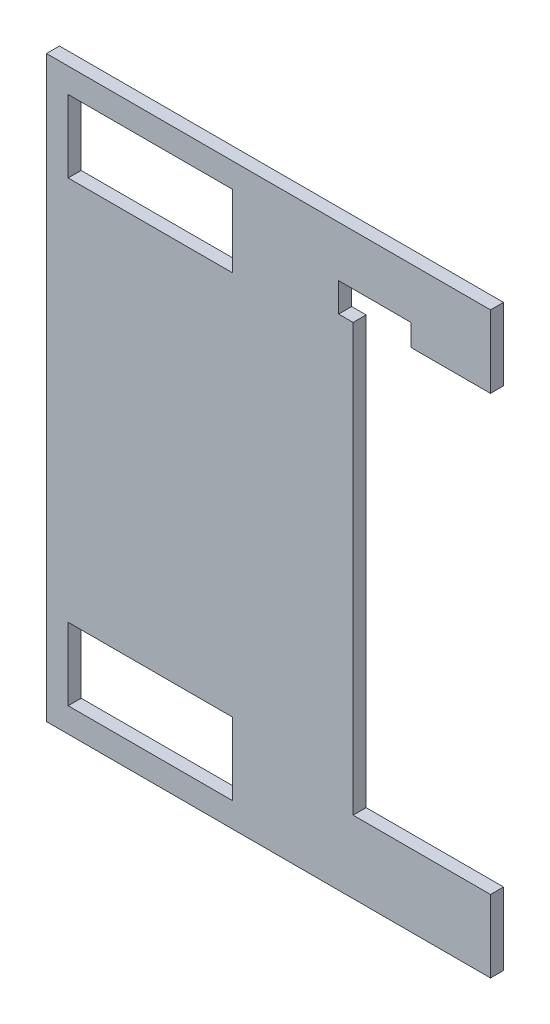
SolidWorks part; units mm, degrees
material "Pine"
ref_plane "Front Plane" through (0, 0, 0) normal (0, 0, 1) x (1, 0, 0)
ref_plane "Top Plane" through (0, 0, 0) normal (0, 1, 0) x (1, 0, 0)
ref_plane "Right Plane" through (0, 0, 0) normal (1, 0, 0) x (0, 0, -1)
sketch "Sketch1" plane through (0, 0, 0) normal (0, 0, 1) x (1, 0, 0)
  line L0 (-16.8129, -74.6) -> (-16.8129, 325.4)
  line L1 (-16.8129, 325.4) -> (-323.8122, 325.4)
  line L2 (-323.8122, 325.4) -> (-323.8122, -74.6)
  line L3 (-323.8122, -74.6) -> (-16.8129, -74.6)
  line L9 (-308.8122, 308.4) -> (-195.1729, 308.4)
  line L10 (-308.8122, 308.4) -> (-308.8122, 258.4)
  line L11 (-308.8122, 258.4) -> (-195.1729, 258.4)
  line L12 (-195.1729, 308.4) -> (-195.1729, 258.4)
  line L13 (-308.8122, 308.4) -> (-195.1729, 258.4) construction
  line L14 (-308.8122, 258.4) -> (-195.1729, 308.4) construction
  line L18 (-308.8122, -57.6) -> (-195.1729, -57.6)
  line L19 (-308.8122, -57.6) -> (-308.8122, -7.6)
  line L20 (-308.8122, -7.6) -> (-195.1729, -7.6)
  line L21 (-195.1729, -57.6) -> (-195.1729, -7.6)
  line L22 (-308.8122, -57.6) -> (-195.1729, -7.6) construction
  line L23 (-308.8122, -7.6) -> (-195.1729, -57.6) construction
  point P16 (-251.9926, 283.4)
  point P27 (-251.9926, -32.6)
  dimension "D2" = 50
  dimension "D3" = 17
  dimension "D5" = 15
  dimension "D6" = 15
extrude "Boss-Extrude1" add sketch "Sketch1" along normal blind 9
sketch "Sketch2" plane through (0, 0, 0) normal (0, 0, -1) x (-1, 0, 0)
  line L0 (111.8129, -24.6) -> (111.8129, 275.4)
  line L1 (16.8129, 325.4) -> (111.8129, 325.4)
  line L2 (16.8129, 325.4) -> (16.8129, 275.4)
  line L3 (16.8129, 275.4) -> (111.8129, 275.4)
  line L4 (111.8129, 325.4) -> (111.8129, 275.4)
  line L5 (16.8129, 325.4) -> (111.8129, 275.4) construction
  line L6 (16.8129, 275.4) -> (111.8129, 325.4) construction
  line L7 (16.8129, -74.6) -> (111.8129, -74.6)
  line L8 (16.8129, -74.6) -> (16.8129, -24.6)
  line L9 (16.8129, -24.6) -> (111.8129, -24.6)
  line L10 (111.8129, -74.6) -> (111.8129, -24.6)
  line L11 (16.8129, -74.6) -> (111.8129, -24.6) construction
  line L12 (16.8129, -24.6) -> (111.8129, -74.6) construction
  point P4 (64.3129, 300.4)
  point P10 (64.3129, -49.6)
  line M11 (16.8129, 325.4) -> (16.8129, -74.6)
  dimension "D1" = 50
  dimension "D2" = 50
  dimension "D3" = 95
extrude "Cut-Extrude1" cut sketch "Sketch2" against normal through all contours L9 L0 L3 M11 region at (-64.3129, 125.4, 0)
sketch "Sketch3" plane through (0, 0, 0) normal (0, 0, -1) x (-1, 0, 0)
  line L1 (111.8129, 275.4) -> (71.8129, 275.4)
  line L2 (111.8129, 275.4) -> (111.8129, 290.4)
  line L3 (111.8129, 290.4) -> (71.8129, 290.4)
  line L4 (71.8129, 275.4) -> (71.8129, 290.4)
  dimension "D1" = 40
  dimension "D2" = 15
extrude "Cut-Extrude2" cut sketch "Sketch3" against normal blind 10
sketch "Sketch4" plane through (0, 0, 0) normal (0, 0, -1) x (-1, 0, 0)
  line L1 (111.8129, 290.4) -> (121.8129, 290.4)
  line L2 (111.8129, 290.4) -> (111.8129, 270.4)
  line L3 (111.8129, 270.4) -> (121.8129, 270.4)
  line L4 (121.8129, 290.4) -> (121.8129, 270.4)
  dimension "D1" = 10
  dimension "D2" = 20
extrude "Cut-Extrude3" cut sketch "Sketch4" against normal blind 100
